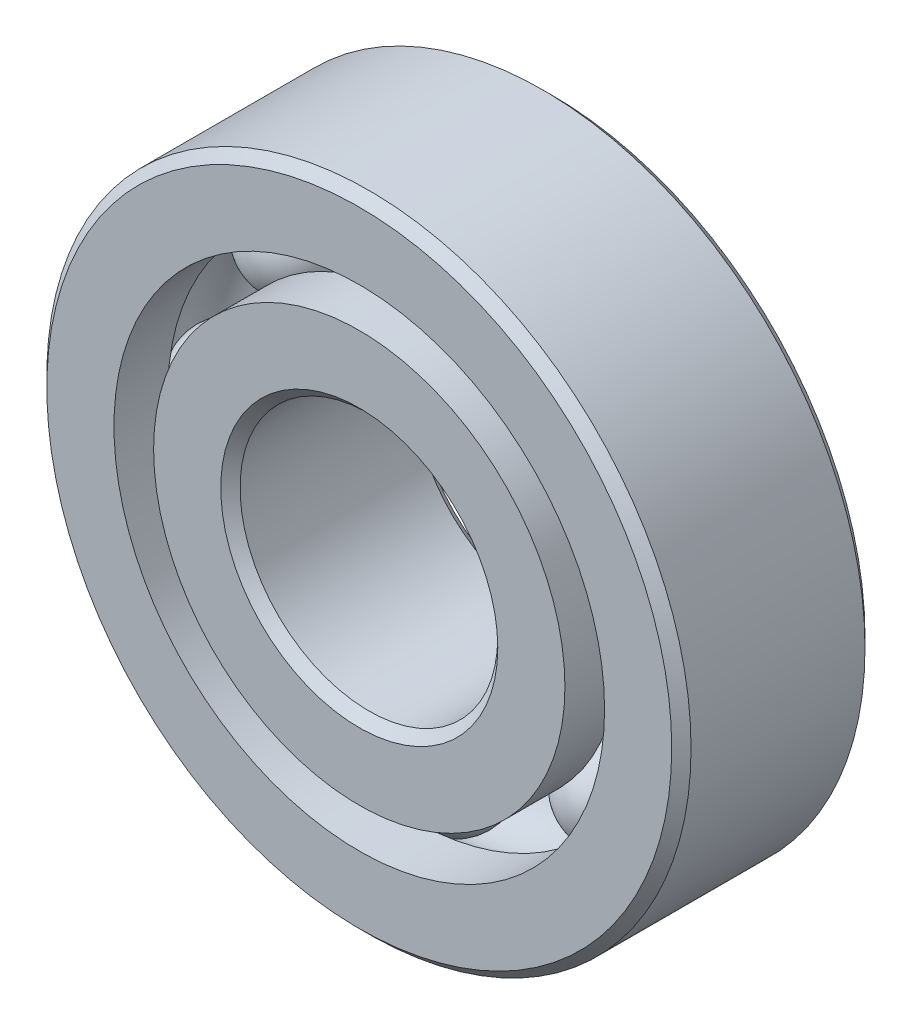
SolidWorks part; units mm, degrees
ref_plane "Front Plane" through (0, 0, 0) normal (0, 0, 1) x (1, 0, 0)
ref_plane "Top Plane" through (0, 0, 0) normal (0, 1, 0) x (1, 0, 0)
ref_plane "Right Plane" through (0, 0, 0) normal (1, 0, 0) x (0, 0, -1)
sketch "Sketch1" plane through (0, 0, 0) normal (1, 0, 0) x (0, 0, -1)
  line L0 (-2.3812, 0) -> (2.3812, 0) construction
  line L1 (0, 7.9375) -> (0, -7.9375) construction
  line L2 (2.1431, 7.9375) -> (-2.1431, 7.9375)
  line L3 (-2.1431, 7.9375) -> (-2.3813, 7.6994)
  line L4 (-2.3813, 7.6994) -> (-2.3813, 6.0447)
  line L5 (-2.3813, 6.0447) -> (-1.0583, 6.0447)
  line L6 (2.3813, 6.0447) -> (1.0583, 6.0447)
  line L7 (2.3813, 7.6994) -> (2.3813, 6.0447)
  line L8 (2.1431, 7.9375) -> (2.3813, 7.6994)
  line L9 (0, 7.9375) -> (0, 5.5562) construction
  line L10 (0, 5.5562) -> (0, 3.175) construction
  arc A0 (-1.0583, 6.0447) -> (1.0583, 6.0447) centre (0, 5.5562) cw
  point P14 (0, 3.175)
  dimension "Width" = 4.7625
  dimension "OD" = 15.875
  dimension "D1" = 45
  dimension "D2" = 0.2381
  dimension "Shaft Dia" = 6.35
  dimension "D3" = 2.1167
  dimension "D4" = 0.4885
revolve "Revolve1" add sketch "Sketch1" angle 360 about L0
sketch "Sketch3" plane through (0, 0, 0) normal (1, 0, 0) x (0, 0, -1)
  line L0 (-2.3813, 5.0678) -> (-1.0583, 5.0678)
  line L1 (0, 7.9375) -> (0, -7.9375) construction
  line L2 (-2.3813, 7.6994) -> (-2.3813, 6.0447) construction
  line L3 (-2.3813, 5.0678) -> (-2.3813, 3.4131)
  line L4 (-2.1431, 7.9375) -> (-2.3813, 7.6994) construction
  line L5 (-2.3813, 3.4131) -> (-2.1431, 3.175)
  line L6 (-2.1431, 3.175) -> (2.1431, 3.175)
  line L7 (2.1431, 7.9375) -> (2.1431, -7.9375) construction
  line L8 (2.1431, 3.175) -> (2.3813, 3.4131)
  line L9 (2.3813, -7.6994) -> (2.3813, 7.6994) construction
  line L10 (2.3813, 3.4131) -> (2.3813, 5.0678)
  line L11 (2.3813, 5.0678) -> (1.0583, 5.0678)
  line L13 (2.1431, 7.9375) -> (2.3813, 7.6994) construction
  arc A0 (1.0583, 6.0447) -> (-1.0583, 6.0447) centre (0, 5.5562) ccw construction
  arc A1 (1.0583, 5.0678) -> (-1.0583, 5.0678) centre (0, 5.5562) cw
revolve "Revolve3" add sketch "Sketch3" angle 360 about L0
sketch "Sketch4" plane through (0, 0, 0) normal (1, 0, 0) x (0, 0, -1)
  line L0 (-1.1656, 5.5562) -> (1.1656, 5.5562)
  arc A2 (-1.1656, 5.5562) -> (1.1656, 5.5562) centre (0, 5.5562) cw
  arc A3 (1.0583, 6.0447) -> (-1.0583, 6.0447) centre (0, 5.5562) ccw construction
revolve "Revolve4" add sketch "Sketch4" angle 360 about L0
ref_axis "Axis1" through (0, 0, -2.3812) along (0, 0, 1)
pattern_circular "CirPattern1" count 8 over 360 about axis through (0, 0, -2.3812) along (0, 0, 1) of bodies 104
sketch "Sketch5" plane through (0, 0, 0) normal (1, 0, 0) x (0, 0, -1)
  line L0 (-2.3813, 6.0447) -> (-1.0583, 6.0447) construction
  line L1 (-2.2622, 6.0447) -> (-1.1656, 6.0447)
  line L2 (-2.2622, 6.0447) -> (-2.2622, 5.0678)
  line L3 (-2.2622, 5.0678) -> (-1.1656, 5.0678)
  line L4 (-1.1656, 6.0447) -> (-1.1656, 5.0678)
  line L5 (-2.3813, 5.0678) -> (-1.0583, 5.0678) construction
  line L6 (2.3813, 6.0447) -> (1.0583, 6.0447) construction
  line L7 (2.2622, 6.0447) -> (1.1656, 6.0447)
  line L8 (2.2622, 6.0447) -> (2.2622, 5.0678)
  line L9 (2.2622, 5.0678) -> (1.1656, 5.0678)
  line L10 (1.1656, 6.0447) -> (1.1656, 5.0678)
  line L11 (2.3813, 5.0678) -> (1.0583, 5.0678) construction
  line L12 (-2.1431, 7.9375) -> (-2.3813, 7.6994) construction
  point P18 (-2.2622, 7.8184)
revolve "Revolve5" [suppressed] add sketch "Sketch5" angle 360 about L0
equation "\"D2@Sketch1\" = \"Width@Sketch1\"*.05"
equation "\"D3@Sketch1\" = \"Width@Sketch1\"/2.25"
equation "\"D4@Sketch1\" = (((\"OD@Sketch1\"-\"Width@Sketch1\")/2)/3.25)/3.5"
equation "\"D2@CirPattern1\" = 360/\"Balls@CirPattern1\""
